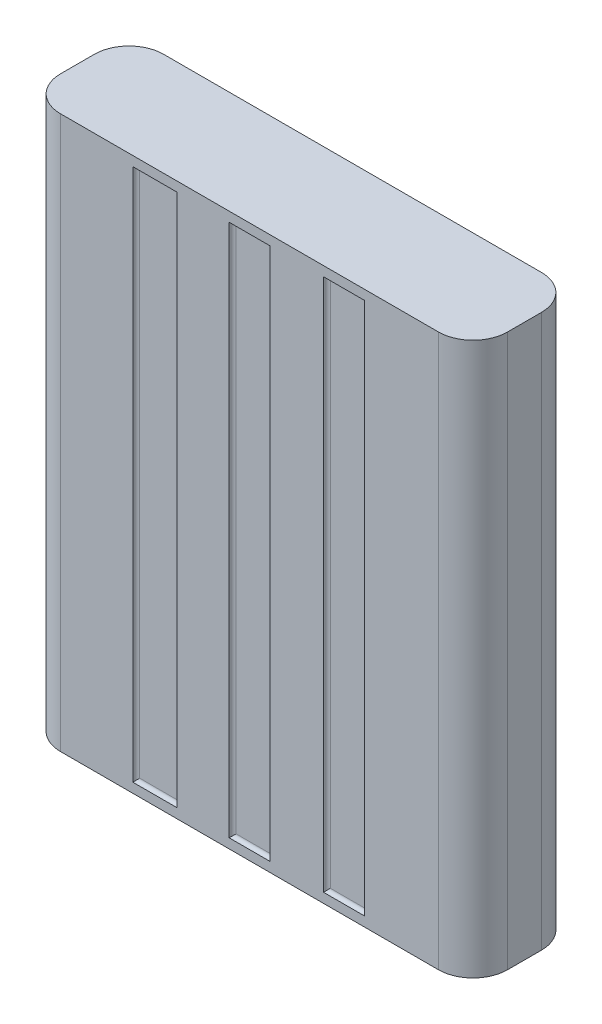
SolidWorks part; units mm, degrees
ref_plane "Front Plane" through (0, 0, 0) normal (0, 0, 1) x (1, 0, 0)
ref_plane "Top Plane" through (0, 0, 0) normal (0, 1, 0) x (1, 0, 0)
ref_plane "Right Plane" through (0, 0, 0) normal (1, 0, 0) x (0, 0, -1)
sketch "Sketch1" plane through (0, 0, 0) normal (0, 1, 0) x (1, 0, 0)
  line L1 (-6.4751, 1.4928) -> (6.4751, 1.4928)
  line L2 (-6.4751, 1.4928) -> (-6.4751, -1.4928)
  line L3 (-6.4751, -1.4928) -> (6.4751, -1.4928)
  line L4 (6.4751, 1.4928) -> (6.4751, -1.4928)
  line L5 (-6.4751, 1.4928) -> (6.4751, -1.4928) construction
  line L6 (-6.4751, -1.4928) -> (6.4751, 1.4928) construction
  point P0 (0, 0)
extrude "Boss-Extrude1" add sketch "Sketch1" along normal blind 16
fillet "Fillet1" radius 1 4 edges at (6.4751, 8, -1.4928) (6.4751, 8, 1.4928) (-6.4751, 8, -1.4928) (-6.4751, 8, 1.4928)
sketch "Sketch2" plane through (0, 0, -1.4928) normal (0, 0, -1) x (-1, 0, 0)
  line L0 (5.4751, 0) -> (5.4751, 16) construction
  line L1 (-5.4751, 10.8394) -> (5.4751, 10.8394)
  line L2 (-5.4751, 10.8394) -> (-5.4751, 10.567)
  line L3 (-5.4751, 10.567) -> (5.4751, 10.567)
  line L4 (5.4751, 10.8394) -> (5.4751, 10.567)
  line L5 (-5.4751, 16) -> (-5.4751, 0) construction
  point P6 (-5.4751, 10.567)
extrude "Boss-Extrude2" add sketch "Sketch2" along normal blind 0.1
fillet "Fillet2" radius 0.1 4 edges at (0, 10.8394, -1.5928) (-5.4751, 10.7032, -1.5928) (0, 10.567, -1.5928) (5.4751, 10.7032, -1.5928)
sketch "Sketch5" plane through (0, 0, -1.5928) normal (0, 0, -1) x (-1, 0, 0)
  line L0 (-5.4751, 10.8394) -> (-5.3751, 10.7394) construction
  line L3 (-5.3751, 10.567) -> (5.4751, 10.567)
  line L4 (5.4751, 10.7394) -> (5.4751, 10.567)
  line L5 (-5.3751, 10.567) -> (-5.4751, 10.567)
  line L7 (-5.3751, 10.8394) -> (-5.4751, 10.8394)
  line L8 (-5.4751, 10.567) -> (-5.4751, 10.8394)
  line L9 (-5.4751, 10.8394) -> (-5.4751, 10.567) construction
  line L11 (-5.3751, 10.8394) -> (5.4751, 10.8394)
  line L14 (5.4751, 10.8394) -> (5.4751, 10.7394)
extrude "Cut-Extrude2" cut sketch "Sketch5" against normal blind 0.1
sketch "Sketch6" plane through (0, 0, -1.4928) normal (0, 0, -1) x (-1, 0, 0)
  line L8 (-3.3309, 15.7209) -> (-2.1442, 15.7209)
  line L9 (-3.3309, 15.7209) -> (-3.3309, 0.2791)
  line L10 (-3.3309, 0.2791) -> (-2.1442, 0.2791)
  line L11 (-2.1442, 15.7209) -> (-2.1442, 0.2791)
  line L14 (-0.5877, 15.7209) -> (0.5877, 15.7209)
  line L15 (-0.5877, 15.7209) -> (-0.5877, 0.2791)
  line L16 (-0.5877, 0.2791) -> (0.5877, 0.2791)
  line L17 (0.5877, 15.7209) -> (0.5877, 0.2791)
  line L20 (2.0968, 15.7209) -> (3.3783, 15.7209)
  line L21 (2.0968, 15.7209) -> (2.0968, 0.2791)
  line L22 (2.0968, 0.2791) -> (3.3783, 0.2791)
  line L23 (3.3783, 15.7209) -> (3.3783, 0.2791)
  point P10 (-2.7375, 8)
  point P22 (2.7375, 8)
extrude "Cut-Extrude3" cut sketch "Sketch6" against normal blind 0.1 contours L23 L22 L21 L20 | L17 L16 L15 L14 | L11 L10 L9 L8
sketch "Sketch10" plane through (0, 0, 1.4928) normal (0, 0, 1) x (1, 0, 0)
  line L1 (3.3309, 15.7209) -> (2.1442, 15.7209)
  line L2 (3.3309, 15.7209) -> (3.3309, 0.2791)
  line L3 (3.3309, 0.2791) -> (2.1442, 0.2791)
  line L4 (2.1442, 15.7209) -> (2.1442, 0.2791)
  line L5 (0.5877, 15.7209) -> (-0.5877, 15.7209)
  line L6 (0.5877, 15.7209) -> (0.5877, 0.2791)
  line L7 (0.5877, 0.2791) -> (-0.5877, 0.2791)
  line L8 (-0.5877, 15.7209) -> (-0.5877, 0.2791)
  line L9 (-2.0968, 15.7209) -> (-3.3783, 15.7209)
  line L10 (-2.0968, 15.7209) -> (-2.0968, 0.2791)
  line L11 (-2.0968, 0.2791) -> (-3.3783, 0.2791)
  line L12 (-3.3783, 15.7209) -> (-3.3783, 0.2791)
extrude "Cut-Extrude4" cut sketch "Sketch10" against normal blind 0.1 contours L6 L5 L8 L7 | L2 L1 L4 L3 | L10 L9 L12 L11
fillet "Fillet6" radius 0.1 12 edges at (2.1442, 8, 1.3928) (2.7375, 15.7209, 1.3928) (3.3309, 8, 1.3928) (2.7375, 0.2791, 1.3928) (-0.5877, 8, 1.3928) (0, 15.7209, 1.3928) (0.5877, 8, 1.3928) (0, 0.2791, 1.3928) (-3.3783, 8, 1.3928) (-2.7375, 15.7209, 1.3928) (-2.0968, 8, 1.3928) (-2.7375, 0.2791, 1.3928)
fillet "Fillet7" radius 0.1 12 edges at (-3.3783, 8, -1.3928) (-2.7375, 0.2791, -1.3928) (-2.0968, 8, -1.3928) (-2.7375, 15.7209, -1.3928) (-0.5877, 8, -1.3928) (0, 0.2791, -1.3928) (0.5877, 8, -1.3928) (0, 15.7209, -1.3928) (2.1442, 8, -1.3928) (2.7375, 0.2791, -1.3928) (3.3309, 8, -1.3928) (2.7375, 15.7209, -1.3928)
